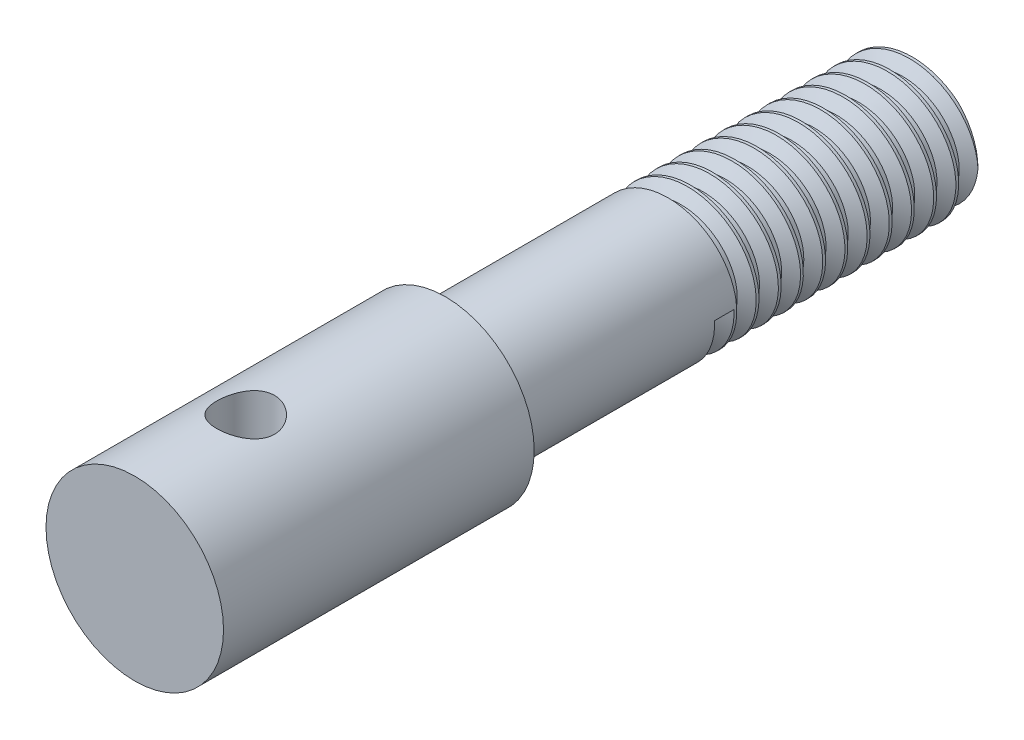
SolidWorks part; units mm, degrees
ref_plane "Alzado" through (0, 0, 0) normal (0, 0, 1) x (1, 0, 0)
ref_plane "Planta" through (0, 0, 0) normal (0, 1, 0) x (1, 0, 0)
ref_plane "Vista lateral" through (0, 0, 0) normal (1, 0, 0) x (0, 0, -1)
sketch "Croquis1" plane through (0, 0, 0) normal (0, 0, 1) x (1, 0, 0)
  circle A0 centre (0, 0) radius 4
  dimension "D1" = 8
extrude "Saliente-Extruir1" add sketch "Croquis1" along normal blind 39
ref_plane "Plano1" through (0, 4, 0) normal (0, 1, 0) x (1, 0, 0)
sketch "Croquis2" plane through (0, 4, 0) normal (0, 1, 0) x (1, 0, 0)
  line L0 (-4, -39) -> (4, -39) construction
  line L1 (-4, 0) -> (-4, -39) construction
  circle A0 centre (0, -34) radius 1.3
  dimension "D1" = 2.6
  dimension "D2" = 5
  dimension "D3" = 4
extrude "Cortar-Extruir1" cut sketch "Croquis2" against normal through all
sketch "Croquis3" plane through (0, 0, 0) normal (0, 0, -1) x (-1, 0, 0)
  circle A0 centre (0, 0) radius 3
  circle A2 centre (0, 0) radius 4
  dimension "D1" = 6
  dimension "D2" = 8
extrude "Cortar-Extruir2" cut sketch "Croquis3" against normal blind 25
thread "Rosca1" pitch 1 method cut profile "Perfil de rosca1" start angle 0, offset 0, length 15, pitch 1, diameter 6
ref_plane "Plano2" through (3, 0, 0) normal (0, -1, 0) x (1, 0, 0)
sketch "Perfil de rosca1" plane through (3, 0, 0) normal (0, -1, 0) x (1, 0, 0)
  line L0 (0, 0) -> (0, 1) construction
  line L11 (0, 0) -> (0, 0.875)
  line L12 (0, 0.875) -> (-0.5413, 0.5625)
  line L13 (-0.5413, 0.5625) -> (-0.5413, 0.3125)
  line L15 (-0.5413, 0.3125) -> (0, 0)
  line L17 (-0.5413, 0.4375) -> (0, 0.4375) construction
  point P2 (0, 0)
  dimension "Pitch" = 1
  dimension "Profile_Angle" = 60
  dimension "Profile_Land" = 0.25
  dimension "Profile_Height" = 0.5413
ref_plane "Plano3" through (0, 4, 0) normal (0, 1, 0) x (1, 0, 0)
sketch "Croquis8" plane through (0, 4, 0) normal (0, 1, 0) x (1, 0, 0)
  line L0 (-10, 0) -> (10, 0)
  line L1 (-10, 0) -> (-10, -4)
  line L2 (-10, -4) -> (10, -4)
  line L3 (10, -4) -> (10, 0)
  line L4 (3, 0) -> (-3, 0) construction
  line L5 (0, 0) -> (0, 3.2967) construction
  dimension "D1" = 4
  dimension "D2" = 20
extrude "Cortar-Extruir3" cut sketch "Croquis8" against normal through all
